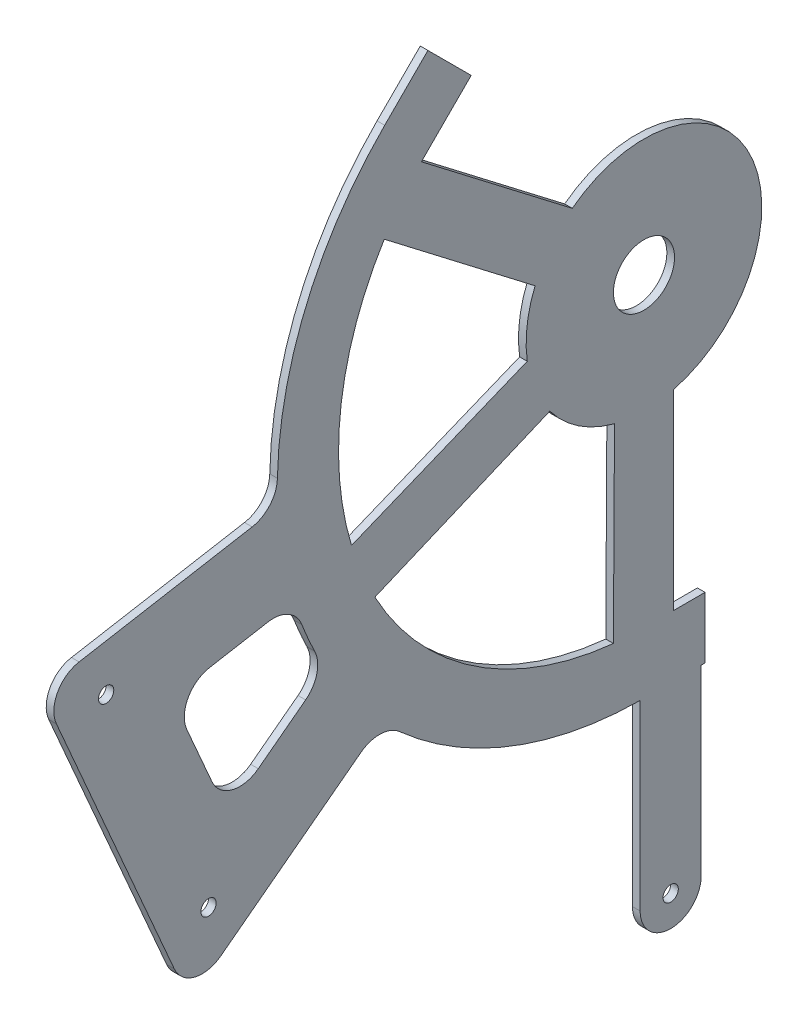
SolidWorks part; units mm, degrees
ref_plane "Front Plane" through (0, 0, 0) normal (0, 0, 1) x (1, 0, 0)
ref_plane "Top Plane" through (0, 0, 0) normal (0, 1, 0) x (1, 0, 0)
ref_plane "Right Plane" through (0, 0, 0) normal (1, 0, 0) x (0, 0, -1)
sketch "Sketch8" plane through (0, 0, 0) normal (1, 0, 0) x (0, 0, -1)
  line L0 (0, 0) -> (-139.7, 0) construction
  circle A1 centre (-272.2355, -114.6296) radius 12.7
  circle A3 centre (-223.5488, -39.2772) radius 3.175
  circle A5 centre (-180.9898, -137.1562) radius 3.175
  circle A7 centre (0, 0) radius 12.7
  circle A9 centre (11.1033, -228.1813) radius 3.175
  circle A10 centre (0, 0) radius 336.7856
  circle A11 centre (0, 0) radius 127
  circle A12 centre (0, 0) radius 152.4
sketch "Sketch9" plane through (0, 0, 0) normal (1, 0, 0) x (0, 0, -1)
  line L0 (0, -126.9544) -> (0, -152.3905)
  line L1 (-89.7703, 89.7703) -> (-107.7564, 107.7564) construction
  line L2 (-98.7633, 98.7633) -> (-80.8028, 116.7239) construction
  line L3 (-107.7564, 107.7564) -> (-89.7959, 125.7169)
  line L4 (-89.7959, 125.7169) -> (-71.8098, 107.7308)
  line L5 (-71.8098, 107.7308) -> (-89.7703, 89.7703)
  arc A0 (-107.7564, 107.7564) -> (0, -152.3905) centre (0, 0) ccw
  arc A1 (-89.7703, 89.7703) -> (0, -126.9544) centre (0, 0) ccw
  point P10 (0, 0)
  dimension "D1" = 25.4
extrude "Boss-Extrude2" add sketch "Sketch9" along normal blind 3.175
sketch "Sketch11" plane through (0, 0, 0) normal (1, 0, 0) x (0, 0, -1)
  line L0 (0, -152.3905) -> (0, -126.9544) construction
  line L1 (0, -152.3905) -> (0, -126.9544)
  line L2 (0, -126.9544) -> (25.4, -126.9544)
  line L3 (25.4, -126.9544) -> (25.4, -152.3905)
  line L4 (25.4, -152.3905) -> (0, -152.3905)
  dimension "D1" = 25.4
extrude "Boss-Extrude4" add sketch "Sketch11" along normal blind 3.175
sketch "Sketch12" plane through (0, 0, 0) normal (1, 0, 0) x (0, 0, -1)
  line L0 (11.1033, -228.1813) -> (11.1033, -152.3905) construction
  line L1 (0, -152.3905) -> (25.4, -152.3905) construction
  line L2 (23.8033, -228.1813) -> (23.8033, -152.3905)
  line L3 (-1.5967, -228.1813) -> (-1.5967, -152.3822)
  line L4 (0, -152.3905) -> (23.8033, -152.3905)
  line L5 (-1.5967, -228.1813) -> (-1.5967, -152.3905) construction
  circle A0 centre (11.1033, -228.1813) radius 3.175 construction
  circle A1 centre (11.1033, -228.1813) radius 3.175
  arc A2 (-107.7564, 107.7564) -> (0, -152.3905) centre (0, 0) ccw construction
  arc A3 (-1.5967, -152.3822) -> (0, -152.3905) centre (0, 0) ccw
  arc A4 (23.8033, -228.1813) -> (-1.5717, -227.3844) centre (11.1033, -228.1813) cw
extrude "Boss-Extrude5" add sketch "Sketch12" along normal blind 3.175 contours A4 L2 L4 A3 L3 A1 region at (0, -194.8352, -11.1033)
sketch "Sketch13" plane through (0, 0, 0) normal (1, 0, 0) x (0, 0, -1)
  line L0 (-223.5488, -39.2772) -> (0, 0) construction
  line L1 (-180.9898, -137.1562) -> (0, 0) construction
  line L2 (-180.9898, -137.1562) -> (-223.5488, -39.2772) construction
  line L3 (-175.9217, -157.2176) -> (-117.6154, -113.0324)
  line L4 (-234.7837, -21.9094) -> (-162.8611, -9.2727)
  line L5 (-195.2389, -152.1598) -> (-244.2327, -39.4819)
  line L6 (-160.3069, -97.5804) -> (-140.627, -82.6667)
  line L7 (-180.5603, -51.066) -> (-156.268, -46.7979)
  line L8 (-179.6241, -92.5226) -> (-190.0092, -68.6385)
  line L9 (-250.6605, -24.6989) -> (74.2878, 32.3941) construction
  line L10 (-188.7972, -166.9748) -> (74.2878, 32.3941) construction
  line L11 (-173.1824, -107.3376) -> (-74.2878, -32.3941) construction
  line L12 (-196.437, -53.8555) -> (-74.2878, -32.3941) construction
  line L13 (-173.1824, -107.3376) -> (-196.437, -53.8555) construction
  line L14 (-188.7972, -166.9748) -> (-250.6605, -24.6989) construction
  circle A0 centre (-180.9898, -137.1562) radius 3.175 construction
  circle A2 centre (-223.5488, -39.2772) radius 3.175 construction
  circle A3 centre (-180.9898, -137.1562) radius 3.175
  circle A5 centre (-223.5488, -39.2772) radius 3.175
  arc A9 (-180.5603, -51.066) -> (-190.0092, -68.6385) centre (-178.3625, -63.5744) ccw
  arc A10 (-160.3069, -97.5804) -> (-179.6241, -92.5226) centre (-167.9775, -87.4585) cw
  arc A11 (-175.9217, -157.2176) -> (-195.2389, -152.1598) centre (-183.5923, -147.0957) cw
  arc A12 (-234.7837, -21.9094) -> (-244.2327, -39.4819) centre (-232.586, -34.4178) ccw
  arc A13 (-152.3613, 2.9868) -> (-142.218, -54.744) centre (0, 0) ccw
  arc A14 (-136.8893, -66.9641) -> (-101.4871, -113.6804) centre (0, 0) ccw
  arc A15 (-117.6154, -113.0324) -> (-101.4871, -113.6804) centre (-109.9449, -123.1544) cw
  arc A16 (-140.627, -82.6667) -> (-136.8893, -66.9641) centre (-148.2975, -72.5448) ccw
  arc A17 (-156.268, -46.7979) -> (-142.218, -54.744) centre (-154.0703, -59.3063) cw
  arc A18 (-162.8611, -9.2727) -> (-152.3613, 2.9868) centre (-165.0588, 3.2357) ccw
  dimension "D1" = 12.7
  dimension "D2" = 12.7
extrude "Boss-Extrude6" add sketch "Sketch13" along normal blind 3.175
sketch "Sketch14" plane through (0, 0, 0) normal (1, 0, 0) x (0, 0, -1)
  line L0 (0, 0) -> (-117.2906, -48.5833) construction
  line L1 (0, 0) -> (0, -126.9544) construction
  line L2 (0, 0) -> (-84.3977, 64.7606) construction
  line L3 (-29.7998, 38.8742) -> (-100.3289, 92.9931)
  line L4 (25.4, -126.9544) -> (0, -126.9544) construction
  line L5 (12.2455, -126.9544) -> (0, -126.9544)
  line L6 (-84.3977, 64.7606) -> (-92.129, 54.6851) construction
  line L8 (12.2455, -47.4265) -> (12.2455, -126.9544)
  line L9 (-84.3977, 64.7606) -> (-76.6664, 74.8362) construction
  line L10 (-12.2455, -47.4265) -> (-12.7, -126.3176)
  line L11 (-100.3289, 92.9931) -> (-115.7914, 72.8419)
  line L12 (-39.1303, -29.4627) -> (-111.8421, -60.0729)
  line L14 (-48.5025, -6.836) -> (-121.5623, -36.6064)
  line L16 (-45.2623, 18.723) -> (-115.7914, 72.8419)
  circle A0 centre (0, 0) radius 12.7 construction
  circle A1 centre (0, 0) radius 12.7
  arc A2 (-89.7703, 89.7703) -> (0, -126.9544) centre (0, 0) ccw construction
  arc A3 (-39.1303, -29.4627) -> (-12.2455, -47.4265) centre (0, 0) ccw
  arc A4 (12.2455, -47.4265) -> (-29.7998, 38.8742) centre (0, 0) ccw
  arc A5 (-45.2623, 18.723) -> (-48.5025, -6.836) centre (0, 0) ccw
  arc A7 (-121.5623, -36.6064) -> (-111.8421, -60.0729) centre (0, 0) ccw
  arc A8 (-12.7, -126.3176) -> (0, -126.9544) centre (0, 0) ccw
  point P9 (-92.3053, 52.8833)
  dimension "D1" = 12.7
  dimension "D2" = 88.9
  dimension "D3" = 60
extrude "Boss-Extrude7" add sketch "Sketch14" along normal blind 3.175
